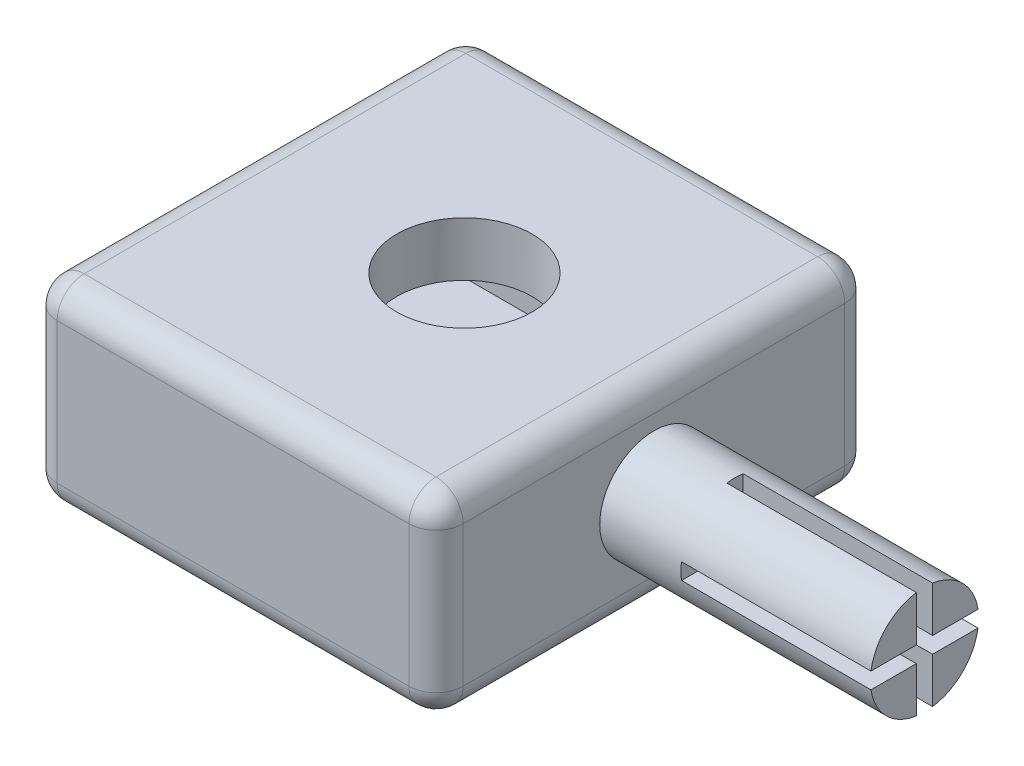
SolidWorks part; units mm, degrees
ref_plane "Front Plane" through (0, 0, 0) normal (0, 0, 1) x (1, 0, 0)
ref_plane "Top Plane" through (0, 0, 0) normal (0, 1, 0) x (1, 0, 0)
ref_plane "Right Plane" through (0, 0, 0) normal (1, 0, 0) x (0, 0, -1)
sketch "Sketch1" plane through (0, 0, 0) normal (0, 1, 0) x (1, 0, 0)
  line L0 (0, 13.1) -> (0, 16.1)
  line L1 (0, 0) -> (15, 0)
  line L2 (0, 0) -> (0, 3)
  line L3 (0, 16.1) -> (15, 16.1)
  line L4 (15, 0) -> (15, 16.1)
  line L5 (0, 13.1) -> (8, 13.1)
  line L7 (0, 3) -> (8, 3)
  arc A0 (8, 3) -> (8, 13.1) centre (8, 8.05) ccw
  point P6 (20, 16.6119)
  point P11 (13.05, 8.05)
  point P12 (0, 0)
  point P13 (0, 0)
  dimension "D2" = 10.1
  dimension "D3" = 5.05
  dimension "D1" = 15
  dimension "D4" = 8
  dimension "D5" = 3
  dimension "D6" = 3
  dimension "D7" = 8
  dimension "D8" = 8.05
extrude "Boss-Extrude1" add sketch "Sketch1" along normal blind 3.2
sketch "Sketch2" plane through (0, 3.2, 0) normal (0, 1, 0) x (1, 0, 0)
  line L1 (15, 16.1) -> (0, 16.1)
  line L2 (15, 16.1) -> (15, 0)
  line L3 (15, 0) -> (0, 0)
  line L4 (0, 16.1) -> (0, 0)
extrude "Boss-Extrude2" add sketch "Sketch2" along normal blind 2
sketch "Sketch3" plane through (0, 0, 0) normal (0, -1, 0) x (1, 0, 0)
  line L1 (0, 0) -> (15, 0)
  line L2 (0, 0) -> (0, -16.1)
  line L3 (0, -16.1) -> (15, -16.1)
  line L4 (15, 0) -> (15, -16.1)
extrude "Boss-Extrude3" add sketch "Sketch3" along normal blind 2
fillet "Fillet1" radius 1 16 edges at (0, -2, -8.05) (15, -2, -8.05) (15, 1.6, -16.1) (0, 1.6, -3) (0, 0, -8.05) (0, 1.6, -13.1) (0, 3.2, -8.05) (0, 1.6, -16.1) (0, 5.2, -8.05) (15, 5.2, -8.05) (15, 1.6, 0) (0, 1.6, 0) (7.5, -2, -16.1) (7.5, 5.2, -16.1) (7.5, 5.2, 0) (7.5, -2, 0)
sketch "Sketch4" plane through (15, 0, 0) normal (1, 0, 0) x (0, 0, -1)
  line L0 (0, -1) -> (0, 4.2) construction
  line L1 (16.1, 4.2) -> (16.1, -1) construction
  line L2 (1, 5.2) -> (15.1, 5.2) construction
  line L3 (15.1, -2) -> (1, -2) construction
  circle A0 centre (8.05, 1.65) radius 2
  dimension "D3" = 4
  dimension "D1" = 8.05
  dimension "D2" = 8.05
  dimension "D4" = 3.55
  dimension "D5" = 3.65
extrude "Boss-Extrude4" add sketch "Sketch4" along normal blind 10
sketch "Sketch5" plane through (25, 0, 0) normal (1, 0, 0) x (0, 0, -1)
  line L0 (8.05, 3.65) -> (8.05, -0.35) construction
  line L1 (6.05, 1.65) -> (10.05, 1.65) construction
  line L2 (6.0726, 1.95) -> (7.75, 1.95)
  line L3 (6.0726, 1.35) -> (7.75, 1.35)
  line L4 (7.75, 3.6274) -> (7.75, 1.95)
  line L5 (8.35, 3.6274) -> (8.35, 1.95)
  line L6 (7.75, 1.35) -> (7.75, -0.3274)
  line L7 (8.35, 1.35) -> (10.0274, 1.35)
  line L8 (8.35, 1.35) -> (8.35, -0.3274)
  line L9 (8.35, 1.95) -> (10.0274, 1.95)
  circle A0 centre (8.05, 1.65) radius 2 construction
  circle A1 centre (8.05, 1.65) radius 2 construction
  arc A2 (6.0726, 1.95) -> (6.0726, 1.35) centre (8.05, 1.65) ccw
  arc A3 (8.35, 3.6274) -> (7.75, 3.6274) centre (8.05, 1.65) ccw
  arc A4 (10.0274, 1.35) -> (10.0274, 1.95) centre (8.05, 1.65) ccw
  arc A5 (7.75, -0.3274) -> (8.35, -0.3274) centre (8.05, 1.65) ccw
  dimension "D1" = 0.3
  dimension "D2" = 0.6
  dimension "D3" = 0.3
  dimension "D4" = 0.6
extrude "Cut-Extrude1" cut sketch "Sketch5" against normal blind 7
sketch "Sketch6" plane through (0, 5.2, 0) normal (0, 1, 0) x (1, 0, 0)
  line L0 (0, 2) -> (0, 14.1) construction
  line L1 (14, 0) -> (1, 0) construction
  circle A0 centre (8, 8.05) radius 2.5
  dimension "D1" = 5
  dimension "D2" = 8
  dimension "D3" = 8.05
extrude "Cut-Extrude2" cut sketch "Sketch6" against normal through all
